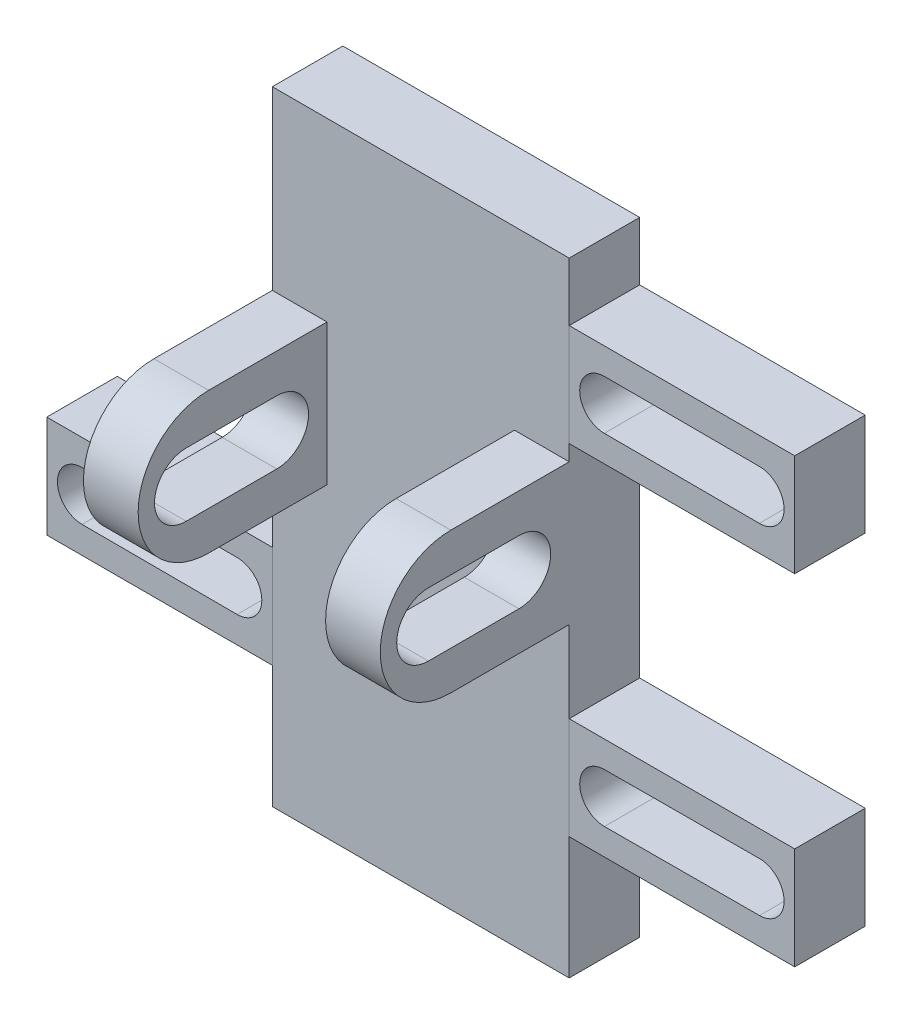
SolidWorks part; units mm, degrees
ref_plane "Front Plane" through (0, 0, 0) normal (0, 0, 1) x (1, 0, 0)
ref_plane "Top Plane" through (0, 0, 0) normal (0, 1, 0) x (1, 0, 0)
ref_plane "Right Plane" through (0, 0, 0) normal (1, 0, 0) x (0, 0, -1)
sketch "Sketch1" plane through (0, 0, 0) normal (0, 0, 1) x (1, 0, 0)
  line L0 (4692.3212, -62.8445) -> (4650.9212, -62.8445) construction
  line L1 (4661.0828, -18.6148) -> (4682.1433, -18.6148)
  line L2 (4661.0828, -18.6148) -> (4661.0828, -62.8445)
  line L3 (4661.0828, -62.8445) -> (4682.1433, -62.8445)
  line L4 (4682.1433, -18.6148) -> (4682.1433, -62.8445)
  line L5 (4661.0828, -27.1456) -> (4658.9212, -27.1456) construction
  line L6 (4658.9212, -12.4285) -> (4658.9212, -50.5381) construction
  line L7 (4682.1433, -34.3161) -> (4684.3037, -34.2412) construction
  line L8 (4684.3037, -50.5381) -> (4684.3037, -12.4285) construction
extrude "Boss-Extrude1" add sketch "Sketch1" along normal blind 5
sketch "Sketch2" plane through (0, 0, 0) normal (0, 0, -1) x (-1, 0, 0)
  line L0 (-4671.6212, -59.6913) -> (-4671.6212, -53.6913) construction
  line L1 (-4664.1212, -59.6913) -> (-4679.1212, -59.6913) construction
  line L2 (-4679.1212, -53.6913) -> (-4664.1212, -53.6913) construction
  line L4 (-4674.1212, -53.8163) -> (-4669.1212, -53.8163)
  line L5 (-4674.1212, -53.8163) -> (-4674.1212, -59.5663)
  line L6 (-4674.1212, -59.5663) -> (-4669.1212, -59.5663)
  line L7 (-4669.1212, -53.8163) -> (-4669.1212, -59.5663)
  line L8 (-4674.1212, -53.8163) -> (-4669.1212, -59.5663) construction
  line L9 (-4674.1212, -59.5663) -> (-4669.1212, -53.8163) construction
  point P6 (-4671.6212, -56.6913)
  dimension "D1" = 5.75
  dimension "D2" = 5
sketch "Sketch4" plane through (4661.0828, 0, 0) normal (-1, 0, 0) x (0, 0, 1)
  line L3 (5, -18.6148) -> (5, -62.8445) construction
  line L4 (13.4005, -31.1292) -> (5, -31.1292)
  line L6 (13.4005, -41.1292) -> (5, -41.1292)
  line L7 (5, -31.1292) -> (5, -41.1292)
  arc A0 (13.4005, -41.1292) -> (13.4005, -31.1292) centre (13.4005, -36.1292) ccw
  dimension "D1" = 5
extrude "Boss-Extrude3" add sketch "Sketch4" against normal blind 3.8801
sketch "Sketch5" plane through (4664.9629, 0, 0) normal (1, 0, 0) x (0, 0, -1)
  line L0 (-14.9864, -36.1292) -> (-8.5634, -36.1292) construction
  line L1 (-14.9864, -33.8792) -> (-8.5634, -33.8792)
  line L2 (-14.9864, -38.3792) -> (-8.5634, -38.3792)
  line L3 (-13.4005, -36.1292) -> (-8.9343, -36.1292) construction
  arc A1 (-14.9864, -33.8792) -> (-14.9864, -38.3792) centre (-14.9864, -36.1292) ccw
  arc A2 (-8.5634, -38.3792) -> (-8.5634, -33.8792) centre (-8.5634, -36.1292) ccw
  point P3 (-11.7749, -36.1292)
  dimension "D1" = 2.25
  dimension "D2" = 1.6257
  dimension "D3" = 4.8372
extrude "Cut-Extrude1" cut sketch "Sketch5" against normal blind 8
ref_plane "Plane1" through (4671.6131, 0, 0) normal (-1, 0, 0) x (0, 0, 1)
mirror "Mirror2" about plane through (4671.6131, 0, 0) normal (-1, 0, 0) of "Cut-Extrude1", "Boss-Extrude3"
sketch "Sketch6" plane through (0, 0, 5) normal (0, 0, 1) x (1, 0, 0)
  line L0 (4688.3131, -48.9131) -> (4688.3131, -52.1631) construction
  line L1 (4682.1433, -46.9131) -> (4698.1433, -46.9131)
  line L2 (4682.1433, -46.9131) -> (4682.1433, -54.1631)
  line L3 (4682.1433, -54.1631) -> (4698.1433, -54.1631)
  line L4 (4698.1433, -46.9131) -> (4698.1433, -54.1631)
  line L5 (4658.9131, -50.5381) -> (4684.2955, -50.5381) construction
  line L6 (4688.3131, -52.1631) -> (4688.3131, -54.1631) construction
  line L7 (4688.3131, -48.9131) -> (4688.3131, -46.9131) construction
  line L8 (4695.6433, -52.2555) -> (4698.1433, -52.2555) construction
  line L9 (4695.6382, -50.5055) -> (4684.6382, -50.5381) construction
  line L10 (4695.6433, -52.2555) -> (4684.6434, -52.2881)
  line L11 (4695.633, -48.7555) -> (4684.633, -48.7881)
  line L12 (4686.6881, -50.5381) -> (4689.9381, -50.5381) construction
  line L13 (4682.1433, -62.8445) -> (4682.1433, -41.1292) construction
  arc A1 (4695.6433, -52.2555) -> (4695.633, -48.7555) centre (4695.6382, -50.5055) ccw
  arc A2 (4684.633, -48.7881) -> (4684.6434, -52.2881) centre (4684.6382, -50.5381) ccw
  circle A3 centre (4688.3131, -50.5381) radius 1.625 construction
  point P18 (4690.1382, -50.5218)
  dimension "D2" = 11
  dimension "D3" = 16
  dimension "D1" = 1.75
  dimension "D4" = 2.5
extrude "Boss-Extrude4" add sketch "Sketch6" against normal blind 5 separate body
ref_plane "Plane2" through (4671.6131, 0, 0) normal (-1, 0, 0) x (0, 0, 1)
mirror "Mirror3" about plane through (4671.6131, 0, 0) normal (-1, 0, 0) of bodies 107
ref_plane "Plane3" through (0, -24.872, 0) normal (0, -1, 0) x (-1, 0, 0)
sketch "Sketch9" plane through (0, 0, 5) normal (0, 0, 1) x (1, 0, 0)
  line L0 (4671.6131, -62.8445) -> (4671.6131, -18.6148) construction
  line L1 (4661.0828, -62.8445) -> (4682.1433, -62.8445) construction
  line L2 (4682.1433, -18.6148) -> (4661.0828, -18.6148) construction
  line L3 (4671.6131, -40.7297) -> (4677.5932, -40.7297) construction
ref_plane "Plane4" through (0, -40.7297, 0) normal (0, -1, 0) x (-1, 0, 0)
sketch "Sketch10" plane through (0, 0, 5) normal (0, 0, 1) x (1, 0, 0)
  line L0 (4654.9131, -26.3852) -> (4654.9131, -50.5381) construction
  line L1 (4654.9131, -38.4617) -> (4652.351, -38.4617) construction
ref_plane "Plane5" through (0, -38.4617, 0) normal (0, -1, 0) x (-1, 0, 0)
mirror "Mirror4" about plane through (0, -38.4617, 0) normal (0, -1, 0) of bodies 109 107
sketch "Sketch11" plane through (0, 0, 5) normal (0, 0, 1) x (1, 0, 0)
  line L1 (4645.0828, -22.7602) -> (4661.0828, -22.7602)
  line L2 (4645.0828, -22.7602) -> (4645.0828, -30.0102)
  line L3 (4645.0828, -30.0102) -> (4661.0828, -30.0102)
  line L4 (4661.0828, -22.7602) -> (4661.0828, -30.0102)
extrude "Cut-Extrude2" cut sketch "Sketch11" against normal up to surface (5 mm away) up to face at (4653.088, -26.4015, 0)
